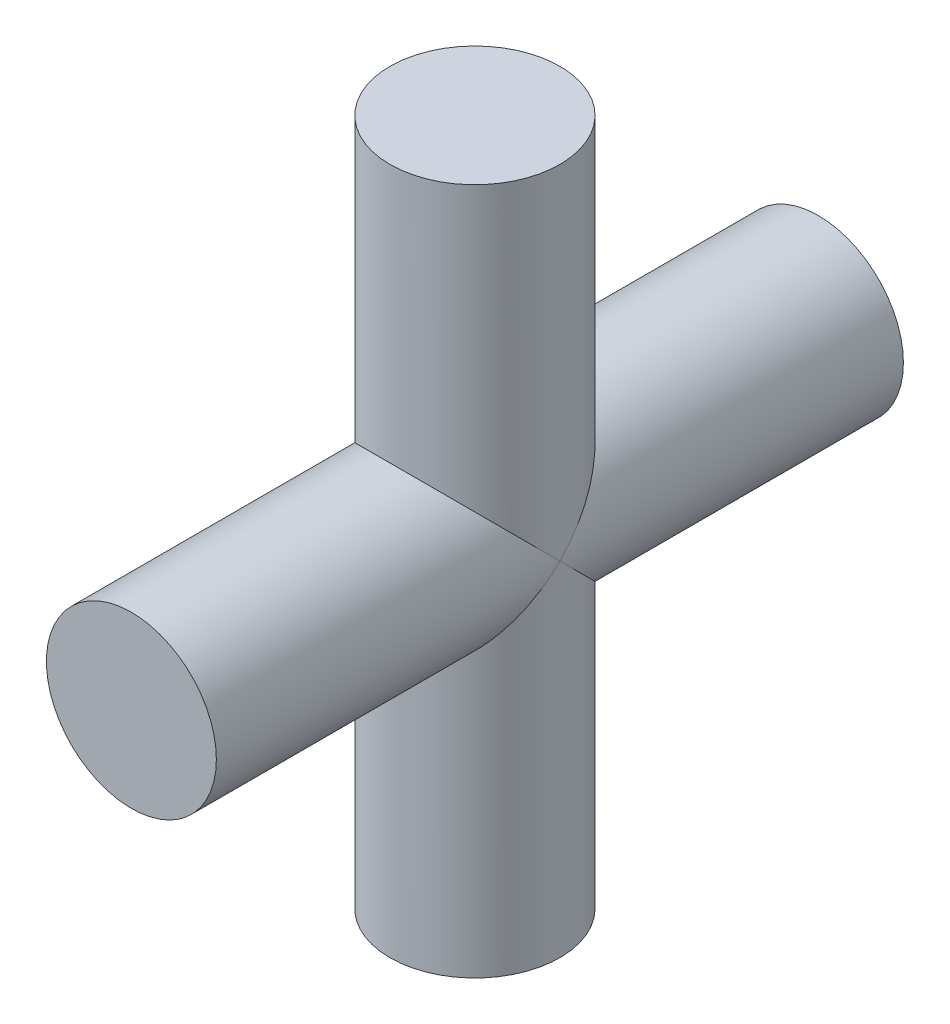
SolidWorks part; units mm, degrees
ref_plane "Front Plane" through (0, 0, 0) normal (0, 0, 1) x (1, 0, 0)
ref_plane "Top Plane" through (0, 0, 0) normal (0, 1, 0) x (1, 0, 0)
ref_plane "Right Plane" through (0, 0, 0) normal (1, 0, 0) x (0, 0, -1)
sketch "Sketch1" plane through (0, 0, 0) normal (0, 0, 1) x (1, 0, 0)
  circle A0 centre (0, 0) radius 4.7
  dimension "D1" = 9.4
extrude "Boss-Extrude1" add sketch "Sketch1" along normal blind 19 and the other way blind 19
sketch "Sketch2" plane through (0, 0, 0) normal (0, 1, 0) x (1, 0, 0)
  circle A0 centre (0, 0) radius 4.7
  dimension "D1" = 9.4
extrude "Boss-Extrude2" add sketch "Sketch2" along normal blind 19 and the other way blind 19
